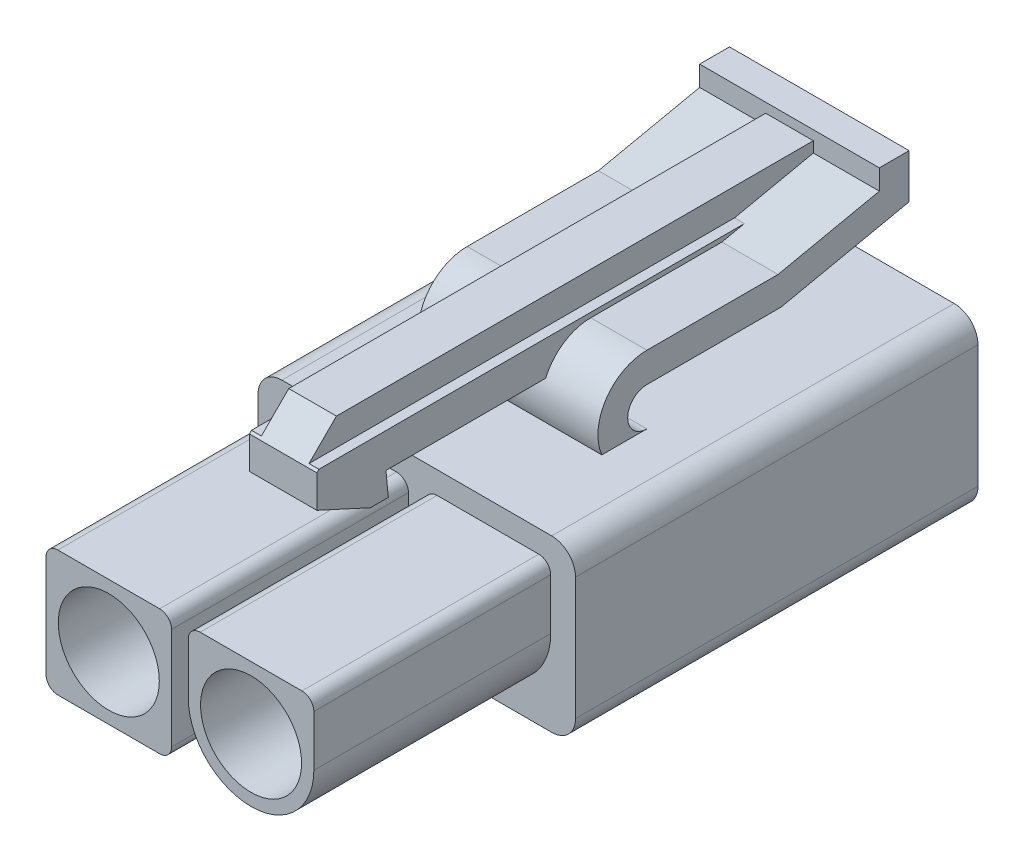
SolidWorks part; units mm, degrees
ref_plane "Front Plane" through (0, 0, 0) normal (0, 0, 1) x (1, 0, 0)
ref_plane "Top Plane" through (0, 0, 0) normal (0, 1, 0) x (1, 0, 0)
ref_plane "Right Plane" through (0, 0, 0) normal (1, 0, 0) x (0, 0, -1)
sketch "Sketch1" plane through (0, 0, 0) normal (0, 0, 1) x (1, 0, 0)
  line L1 (-6.66, -3.57) -> (6.66, -3.57)
  line L2 (-6.66, -3.57) -> (-6.66, 3.57)
  line L3 (-6.66, 3.57) -> (6.66, 3.57)
  line L4 (6.66, -3.57) -> (6.66, 3.57)
  line L5 (-6.66, -3.57) -> (6.66, 3.57) construction
  line L6 (-6.66, 3.57) -> (6.66, -3.57) construction
  point P0 (0, 0)
  dimension "D1" = 7.14
  dimension "D2" = 13.32
extrude "Boss-Extrude1" add sketch "Sketch1" against normal blind 16.89
sketch "Sketch2" plane through (0, 0, 0) normal (0, 0, 1) x (1, 0, 0)
  line L0 (0.35, 2.635) -> (0.35, 0)
  line L1 (-5.62, -2.635) -> (-0.35, -2.635)
  line L2 (-5.62, -2.635) -> (-5.62, 2.635)
  line L3 (-5.62, 2.635) -> (-0.35, 2.635)
  line L4 (-0.35, -2.635) -> (-0.35, 2.635)
  line L5 (-5.62, -2.635) -> (-0.35, 2.635) construction
  line L6 (-5.62, 2.635) -> (-0.35, -2.635) construction
  line L7 (5.62, 0) -> (5.62, 2.635)
  line L8 (5.62, 2.635) -> (0.35, 2.635)
  line L9 (-2.985, 0) -> (2.985, 0) construction
  arc A0 (0.35, 0) -> (5.62, 0) centre (2.985, 0) ccw
  point P0 (-2.985, 0)
  dimension "D1" = 5.27
  dimension "D2" = 11.24
extrude "Boss-Extrude2" add sketch "Sketch2" along normal offset from surface (9.94 mm away) 26.83 up to face at (0, 0, -16.89)
sketch "Sketch3" plane through (0, 0, 0) normal (0, 0, 1) x (1, 0, 0)
  line L0 (2.985, 0) -> (-2.985, 0) construction
  circle A0 centre (2.985, 0) radius 2.12
  circle A1 centre (-2.985, 0) radius 2.12
  dimension "D1" = 4.24
extrude "Cut-Extrude1" cut sketch "Sketch3" against normal through all both and the other way through all
sketch "Sketch4" plane through (0, 0, 0) normal (1, 0, 0) x (0, 0, -1)
  line L0 (5.885, 5.18) -> (11.5212, 5.18)
  line L1 (11.5212, 5.18) -> (16.89, 6.32)
  line L2 (16.89, 6.32) -> (16.89, 8.18)
  line L3 (16.89, 8.18) -> (15.64, 8.18)
  line L4 (15.64, 8.18) -> (15.64, 7.3324)
  line L5 (15.64, 7.3324) -> (11.39, 6.43)
  line L6 (11.39, 6.43) -> (5.885, 6.43)
  line L7 (16.89, 3.57) -> (0, 3.57) construction
  line L8 (3.9942, 3.57) -> (5.885, 3.57)
  line L9 (16.89, -3.57) -> (0, -3.57) construction
  line L10 (3.83, 4.375) -> (16.89, 4.375) construction
  line L11 (16.89, 4.375) -> (16.89, 6.32) construction
  line L12 (7.1795, 6.43) -> (7.1795, 5.18) construction
  line L13 (12.2207, 6.6064) -> (12.4803, 5.3837) construction
  line L14 (16.89, -3.57) -> (16.89, 3.57) construction
  arc A0 (5.885, 6.43) -> (3.9942, 3.57) centre (5.885, 4.375) ccw
  arc A1 (5.885, 5.18) -> (5.885, 3.57) centre (5.885, 4.375) ccw
  point P24 (15.64, 6.7644)
  point P25 (0, 0)
  point P26 (10.9114, 6.43)
  point P27 (6.0706, 6.43)
  point P28 (5.2975, 3.57)
  point P29 (3.9173, 3.57)
  dimension "D1" = 1.25
  dimension "D2" = 10
  dimension "D3" = 13.06
  dimension "D4" = 11.75
  dimension "D5" = 2.75
  dimension "D6" = 5.5
extrude "Boss-Extrude3" add sketch "Sketch4" along normal mid plane 7.54
sketch "Sketch5" plane through (0, 0, 0) normal (1, 0, 0) x (0, 0, -1)
  line L0 (15.64, 7.78) -> (-4.3726, 7.78)
  line L1 (15.64, 8.18) -> (15.64, 7.3324) construction
  line L2 (-4.3726, 7.78) -> (-5.61, 6.5426)
  line L3 (-5.61, 6.5426) -> (-5.61, 5.18)
  line L4 (-5.61, 5.18) -> (-3.36, 4.15)
  line L6 (-2.71, 5.18) -> (5.5032, 5.18)
  line L7 (5.5032, 5.18) -> (15.64, 7.3324)
  line L8 (15.64, 7.3324) -> (15.64, 7.78)
  line L9 (15.64, 7.3324) -> (11.39, 6.43) construction
  line L11 (5.885, 5.18) -> (11.5212, 5.18) construction
  line L12 (16.89, 6.32) -> (16.89, 8.18) construction
  line L13 (-3.36, 4.15) -> (-2.61, 4.15)
  line L14 (-2.61, 4.15) -> (-2.71, 5.18)
  point P12 (-2.6657, 3.8488)
  point P13 (-3.3229, 5.18)
  point P14 (-3.4637, 4.15)
  dimension "D1" = 2.6
  dimension "D2" = 22.5
  dimension "D3" = 135
  dimension "D4" = 1.75
  dimension "D5" = 3.63
  dimension "D6" = 3
  dimension "D7" = 2.9
  dimension "D8" = 0.75
extrude "Boss-Extrude4" add sketch "Sketch5" along normal mid plane 2.83
sketch "Sketch7" plane through (-1.415, 0, 0) normal (-1, 0, 0) x (0, 0, 1)
  line L0 (4.3726, 7.78) -> (5.61, 6.5426) construction
  line L1 (-15.64, 7.78) -> (4.3726, 7.78) construction
  line L2 (-15.64, 7.3324) -> (-15.64, 7.78) construction
  line L3 (-11.39, 6.43) -> (-15.64, 7.3324) construction
  line L4 (4.3726, 7.78) -> (5.5226, 6.63)
  line L5 (-15.64, 7.78) -> (4.3726, 7.78)
  line L6 (-15.64, 7.3324) -> (-15.64, 7.78)
  line L7 (-12.3319, 6.63) -> (-15.64, 7.3324)
  line L8 (5.5226, 6.63) -> (-12.3319, 6.63)
  dimension "D1" = 1.45
extrude "Cut-Extrude3" cut sketch "Sketch7" against normal blind 0.415
sketch "Sketch8" plane through (1.415, 0, 0) normal (1, 0, 0) x (0, 0, -1)
  line L5 (-4.3726, 7.78) -> (-5.5226, 6.63)
  line L6 (-5.5226, 6.63) -> (12.3319, 6.63)
  line L7 (12.3319, 6.63) -> (15.64, 7.3324)
  line L8 (15.64, 7.3324) -> (15.64, 7.78)
  line L9 (15.64, 7.78) -> (-4.3726, 7.78)
  line L10 (-4.3726, 7.78) -> (-5.5226, 6.63)
  line L11 (-5.5226, 6.63) -> (12.3319, 6.63)
  line L12 (12.3319, 6.63) -> (15.64, 7.3324)
  line L13 (15.64, 7.3324) -> (15.64, 7.78)
  line L14 (15.64, 7.78) -> (-4.3726, 7.78)
  dimension "D1" = 0
extrude "Cut-Extrude4" cut sketch "Sketch8" against normal blind 0.415
fillet "Fillet1" radius 1 4 edges at (6.66, 3.57, -8.445) (6.66, -3.57, -8.445) (-6.66, -3.57, -8.445) (-6.66, 3.57, -8.445)
fillet "Fillet2" radius 0.5 6 edges at (-5.62, -2.635, 4.97) (-0.35, -2.635, 4.97) (-5.62, 2.635, 4.97) (-0.35, 2.635, 4.97) (0.35, 2.635, 4.97) (5.62, 2.635, 4.97)
